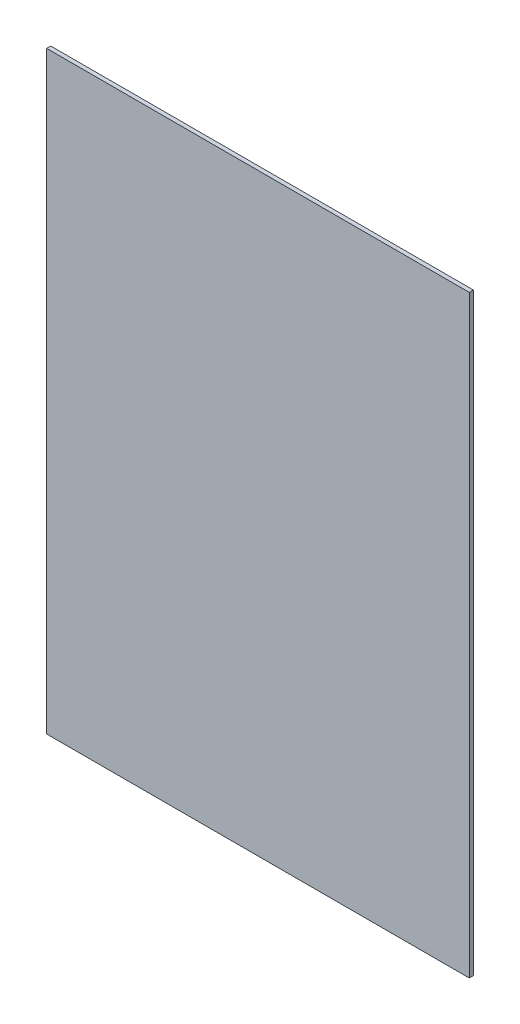
SolidWorks part; units mm, degrees
ref_plane "Спереди" through (0, 0, 0) normal (0, 0, 1) x (1, 0, 0)
ref_plane "Сверху" through (0, 0, 0) normal (0, 1, 0) x (1, 0, 0)
ref_plane "Справа" through (0, 0, 0) normal (1, 0, 0) x (0, 0, -1)
other "Configuration Table"
sketch "Эскиз1" plane through (0, 0, 0) normal (0, 0, 1) x (1, 0, 0)
  line L2 (-1138.3, -435.8) -> (-518, -435.8)
  line L3 (-1138.3, -435.8) -> (-1138.3, 435.8)
  line L4 (-1138.3, 435.8) -> (-518, 435.8)
  line L5 (-518, -435.8) -> (-518, 435.8)
extrude "Бобышка-Вытянуть1" add sketch "Эскиз1" against normal blind 6
equation "\"Глубина груза\"= 490"
equation "\"Высота груза\"= 297"
equation "\"Ширина ячейки\"= \"Ширина груза\" + 10"
equation "\"Глубина ячейки\"= \"Глубина груза\" + 10"
equation "\"Высота ячейки\"= \"Высота груза\" + 10 + 13"
equation "\"Колво ячеек ширина\"= 2"
equation "\"Колво ячеек высота\"= 2"
equation "\"Толщина стенки\" = 6"
equation "\"Крепление дверцы\"= 5 "
equation "\"Ширина рейки\"= \"Толщина шестерни\""
equation "\"Высота рейки\"= 20"
equation "\"Высота пола\"= \"Толщина стенки\" * 2"
equation "\"Колво полозьев\"= 5"
equation "\"Отступ рейки\"= 20"
equation "\"Глубина каретки\"= \"Глубина ячейки\" + 30 + \"Мотор Y высота корпуса\" + 20"
equation "\"Длинна рейки\"= ( \"Ширина ячейки\" + \"Толщина стенки\" + \"Крепление дверцы\" ) * \"Колво ячеек ширина\" + \"Ширина ячейки выгрузки\" * \"Колво выгрузки\" + \"Толщина стенки\""
equation "\"Отступ шпильки\"= 26"
equation "\"Диаметр шпильки\"= 5"
equation "\"Длинна шпильки\"= ( \"Высота ячейки\" + \"Толщина стенки\" + \"Высота пола\" ) * \"Колво ячеек высота\" + ( \"Толщина стенки\" + \"Отступ рейки\" ) * 2 "
equation "\"Ширина пластины\"= 50  "
equation "\"Высота зона выгрузки\"= \"Высота ячейки\" * 2 + \"Толщина стенки\" * 2"
equation "\"Колво выгрузки\"= 1"
equation "\"Ширина ячейки выгрузки\"= \"Ширина ячейки\" + \"Толщина стенки\" + \"Отступ крепления мотора фиксации\"*2"
equation "\"Отступ крепления мотора фиксации\" = 30"
equation "\"Мотор X ширина корпуса\"= 42.3"
equation "\"Мотор X высота корпуса\"= 42.3"
equation "\"Мотор X длина корпуса\"= 40"
equation "\"Мотор X вылет вала\"= 19.8"
equation "\"Мотор Y ширина корпуса\"= 42.3"
equation "\"Мотор Y высота корпуса\"= 42.3"
equation "\"Мотор Y длина корпуса\"= 48"
equation "\"Мотор Y вылет вала\"= 30"
equation "\"Мотор Z ширина корпуса\"= 42"
equation "\"Мотор Z высота корпуса\"= 42"
equation "\"Мотор Z длина корпуса\"= 40"
equation "\"Мотор Z вылет вала\"= 23"
equation "\"Мотор диаметр вала ПРЕДВ\"= 5"
equation "\"Мотор шаг крепления ПРЕДВ\"= 31"
equation "\"Мотор диаметр отверстий ПРЕДВ\"= 3"
equation "\"Мотор глубина отверстий ПРЕДВ\"= 4.5"
equation "\"Мотор диаметр буртика ПРЕДВ\"= 22"
equation "\"Мотор высота буртика ПРЕДВ\"= 2"
equation "\"Мотор диаметр шкива ПРЕДВ\"= 16"
equation "\"Мотор длина шкива ПРЕДВ\"= 12"
equation "\"Мотор отступ шкива ПРЕДВ\"= 5"
equation "\"Мотор X шаг градусов\"= 1.8"
equation "\"Мотор Y шаг градусов\"= 1.8"
equation "\"Мотор Z шаг градусов\"= 1.8"
equation "\"Мотор Y диаметр ротора\"= 25.78"
equation "\"Толщина шестерни\"= 10"
equation "\"Ширина груза\"= 420"
equation "\"D1@Бобышка-Вытянуть1\"=\"Толщина стенки\""
